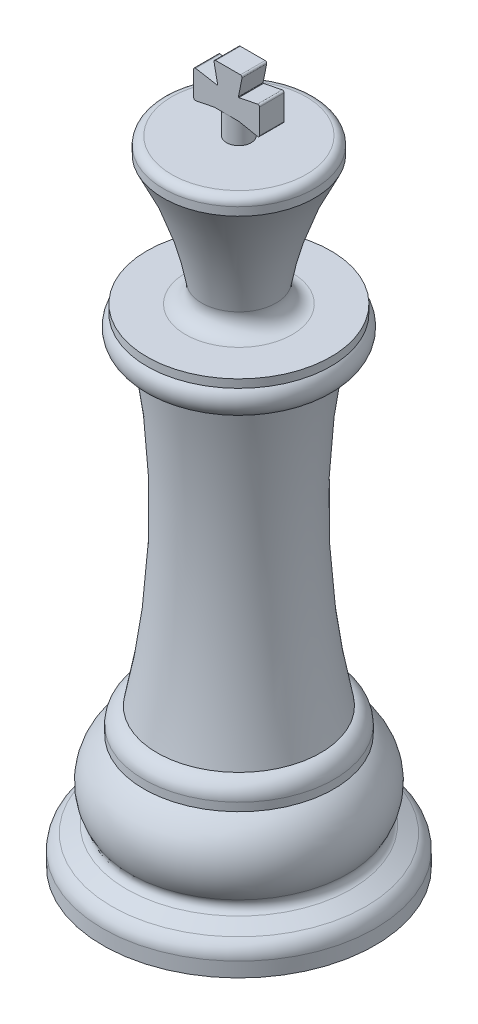
SolidWorks part; units mm, degrees
ref_plane "Front Plane" through (0, 0, 0) normal (0, 0, 1) x (1, 0, 0)
ref_plane "Top Plane" through (0, 0, 0) normal (0, 1, 0) x (1, 0, 0)
ref_plane "Right Plane" through (0, 0, 0) normal (1, 0, 0) x (0, 0, -1)
sketch "Sketch3" plane through (0, 0, 0) normal (0, 0, 1) x (1, 0, 0)
  line L1 (-0.6823, -10.57) -> (13.8724, -10.57)
  line L2 (11.9049, -5.57) -> (15.8724, -7.57)
  line L3 (15.8724, -7.57) -> (15.8724, -10.57)
  line L4 (15.8724, -10.57) -> (13.8724, -10.57)
  line L5 (10.8724, 3.4) -> (10.8724, 4.4)
  line L8 (10.5, 48.72) -> (10.5, 47.72)
  line L17 (-0.6823, 69.43) -> (-0.6823, -10.57)
  line L18 (10.5, 64.43) -> (8.5, 64.43)
  line L19 (8.5, 64.43) -> (8.5, 65.43)
  line L20 (7.5, 66.43) -> (0.8177, 66.43)
  line L22 (0.8177, 66.43) -> (0.8177, 69.43)
  line L23 (0.8177, 69.43) -> (-0.6823, 69.43)
  line L24 (10.5, 48.72) -> (3.5, 48.72)
  arc A0 (10.8724, 3.4) -> (11.9049, -5.57) centre (7.4644, -1.5367) cw
  arc A1 (9.2587, 6.4) -> (10.8724, 4.4) centre (8.8727, 4.4376) cw
  arc A2 (10.5, 47.72) -> (8.5, 44.4) centre (9.0765, 46.3151) cw
  arc A3 (9.2587, 6.4) -> (8.5, 44.4) centre (107.0375, 27.3599) cw
  arc A5 (8.5, 65.43) -> (7.5, 66.43) centre (7.5, 65.43) ccw
  arc A6 (3.5, 48.72) -> (8.5, 64.43) centre (45.8652, 43.8872) cw
  point P15 (0, 63)
  dimension "D9" = 2
  dimension "D10" = 2
  dimension "D11" = 5.9988
  dimension "D13" = 100
  dimension "D16" = 7
  dimension "D15" = 1
  dimension "D2" = 3
  dimension "D3" = 2
  dimension "D4" = 8.97
  dimension "D5" = 1
  dimension "D6" = 2
  dimension "D7" = 3.32
  dimension "D8" = 1
  dimension "D12" = 38
  dimension "D14" = 15.71
  dimension "D17" = 2
  dimension "D18" = 3
  dimension "D19" = 1.5
  dimension "D20" = 80
revolve "Revolve1" add sketch "Sketch3" angle 360 about L17 region at (4.3846, 23.1966, 0)
sketch3d "3DSketch1"
  point P0 (-0.7472, 65.9216, 1.4986)
ref_plane "Plane1" through (0, 0, 1.4986) normal (0, 0, 1) x (1, 0, 0)
sketch "Sketch4" plane through (0, 0, 1.4986) normal (0, 0, 1) x (1, 0, 0)
  line L12 (3.0785, 72.3822) -> (0.8177, 71.93)
  line L14 (-4.4478, 72.3889) -> (-1.8288, 71.93)
  line L15 (3.0785, 68.9778) -> (0.8226, 69.429)
  line L19 (-4.6823, 69.174) -> (-4.6823, 72.1919)
  line L21 (3.3177, 72.186) -> (3.3177, 69.174)
  line L24 (0.8127, 69.43) -> (-2.1774, 69.43)
  line L25 (-2.1872, 69.429) -> (-4.4431, 68.9778)
  line L27 (1.0005, 74.43) -> (-2.0116, 74.43)
  line L36 (1.1966, 74.1908) -> (0.7564, 71.9898)
  line L37 (-2.2077, 74.1908) -> (-1.7675, 71.9898)
  line L38 (-1.8165, 71.93) -> (-1.8288, 71.93)
  line L39 (0.8054, 71.93) -> (0.8177, 71.93)
  arc A0 (-2.2077, 74.1908) -> (-2.0116, 74.43) centre (-2.0116, 74.23) cw
  arc A1 (1.1966, 74.1908) -> (1.0005, 74.43) centre (1.0005, 74.23) ccw
  arc A2 (3.0785, 72.3822) -> (3.3177, 72.186) centre (3.1177, 72.186) cw
  arc A3 (3.3177, 69.174) -> (3.0785, 68.9778) centre (3.1177, 69.174) cw
  arc A4 (-4.4431, 68.9778) -> (-4.6823, 69.174) centre (-4.4823, 69.174) cw
  arc A5 (-4.4478, 72.3889) -> (-4.6823, 72.1919) centre (-4.4823, 72.1919) ccw
  arc A6 (-2.1774, 69.43) -> (-2.1872, 69.429) centre (-2.1774, 69.38) ccw
  arc A7 (0.8226, 69.429) -> (0.8127, 69.43) centre (0.8127, 69.38) ccw
  arc A8 (0.7564, 71.9898) -> (0.8054, 71.93) centre (0.8054, 71.98) ccw
  arc A9 (-1.7675, 71.9898) -> (-1.8165, 71.93) centre (-1.8165, 71.98) cw
  point P2 (-2.2555, 74.43)
  point P8 (1.2445, 74.43)
  point P22 (3.3177, 72.43)
  point P25 (3.3177, 68.93)
  point P28 (-4.6823, 68.93)
  point P31 (-4.6823, 72.43)
  point P34 (-2.1823, 69.43)
  point P37 (0.8177, 69.43)
  point P40 (0.7445, 71.93)
  point P43 (-1.7555, 71.93)
  dimension "D13" = 0.2
  dimension "D14" = 0.05
  dimension "D1" = 3.5
  dimension "D2" = 3.5
  dimension "D3" = 0.5
  dimension "D4" = 0.5
  dimension "D5" = 0.5
  dimension "D6" = 0.5
  dimension "D7" = 3.5
  dimension "D8" = 0
  dimension "D9" = 0.5
  dimension "D10" = 0.5
  dimension "D11" = 2.5
  dimension "D12" = 2.5
extrude "Boss-Extrude1" add sketch "Sketch4" against normal blind 3
fillet "Fillet1" radius 2 1 edges at (-17.237, -7.57, 0)
fillet "Fillet2" radius 1 1 edges at (-13.2695, -5.57, 0)
fillet "Fillet3" radius 2 1 edges at (-4.8646, 48.72, 0)
